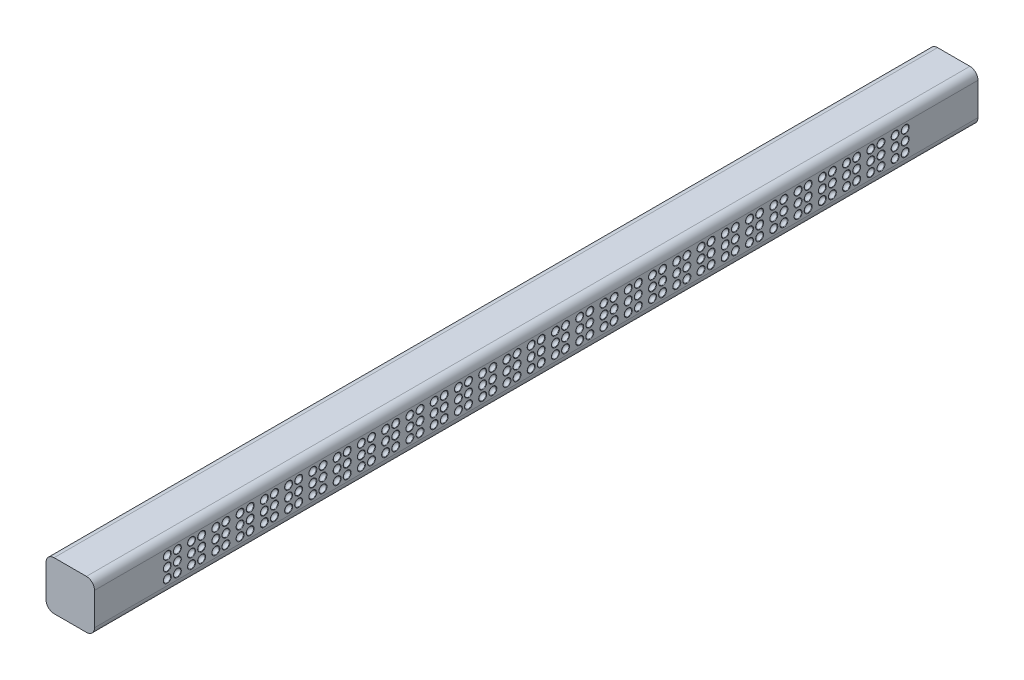
SolidWorks part; units mm, degrees
ref_plane "Front plane" through (0, 0, 0) normal (0, 0, 1) x (1, 0, 0)
ref_plane "Top plane" through (0, 0, 0) normal (0, 1, 0) x (1, 0, 0)
ref_plane "Right Plane" through (0, 0, 0) normal (1, 0, 0) x (0, 0, -1)
sketch "Sketch2" plane through (0, 0, 0) normal (0, 0, 1) x (1, 0, 0)
  line L1 (-4, 6) -> (4, 6)
  line L2 (-6, 4) -> (-6, -4)
  line L3 (-4, -6) -> (4, -6)
  line L4 (6, 4) -> (6, -4)
  arc A0 (-4, 6) -> (-6, 4) centre (-4, 4) ccw
  arc A1 (4, 6) -> (6, 4) centre (4, 4) cw
  arc A2 (4, -6) -> (6, -4) centre (4, -4) ccw
  arc A3 (-6, -4) -> (-4, -6) centre (-4, -4) ccw
  point P8 (6, 0)
  point P16 (0, 6)
  dimension "D3" = 2
  dimension "D1" = 12
extrude "Boss-Extrude1" add sketch "Sketch2" along normal blind 218.5
sketch "Sketch3" plane through (6, 0, 0) normal (1, 0, 0) x (0, 0, -1)
  line L0 (-20.5, -2.5) -> (-20.5, 0) construction
  line L1 (-20.5, -2.5) -> (-18, -2.5) construction
  line L2 (0, -4) -> (0, 4) construction
  circle A0 centre (-20.5, -2.5) radius 0.9
  circle A1 centre (-18, -2.5) radius 0.9
  circle A2 centre (-18, 0) radius 0.9
  circle A3 centre (-18, 2.5) radius 0.9
  circle A4 centre (-20.5, 0) radius 0.9
  circle A5 centre (-20.5, 2.5) radius 0.9
  point P3 (-19.25, -2.5)
  dimension "D5" = 1.8
  dimension "D3" = 2.5
  dimension "D4" = 2.5
  dimension "D6" = 19.25
  dimension "D1" = 2
  dimension "D2" = 3
extrude "Cut-Extrude1" cut sketch "Sketch3" against normal blind 1
fillet "Fillet1" radius 0.9 6 edges at (5, 2.5, 17.1) (5, 2.5, 19.6) (5, 0, 19.6) (5, 0, 17.1) (5, -2.5, 17.1) (5, -2.5, 19.6)
fillet "Fillet2" radius 0.1 6 edges at (6, -2.5, 17.1) (6, -2.5, 19.6) (6, 0, 19.6) (6, 2.5, 19.6) (6, 2.5, 17.1) (6, 0, 17.1)
pattern_linear "LPattern1" count 31 spacing 6 along (0, 0, 1) of "Cut-Extrude1", "Fillet1", "Fillet2"
